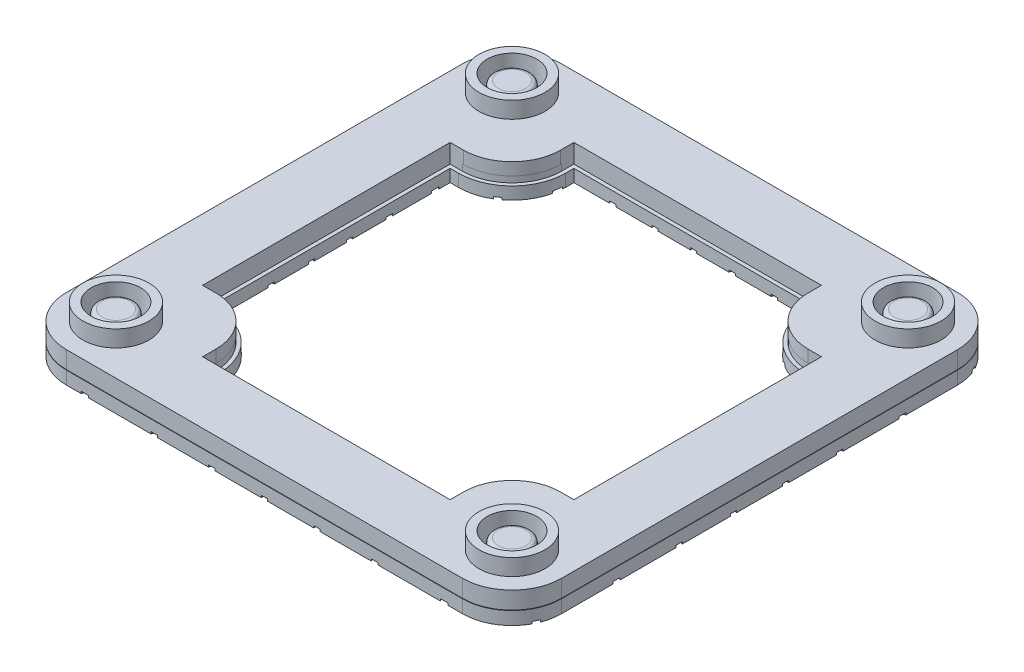
SolidWorks part; units mm, degrees
note: The reader was unsure of these and kept them because the rebuilt part matched: shared geometry of "Sketch3<4>".
ref_plane "Front Plane" through (0, 0, 0) normal (0, 0, 1) x (1, 0, 0)
ref_plane "Top Plane" through (0, 0, 0) normal (0, 1, 0) x (1, 0, 0)
ref_plane "Right Plane" through (0, 0, 0) normal (1, 0, 0) x (0, 0, -1)
sketch "Sketch1" plane through (0, 0, 0) normal (0, 1, 0) x (1, 0, 0)
  line L1 (0, 0) -> (240, 0)
  line L2 (0, 0) -> (0, 240)
  line L3 (0, 240) -> (240, 240)
  line L4 (240, 0) -> (240, 240)
  dimension "D1" = 240
  dimension "D2" = 240
extrude "Boss-Extrude1" add sketch "Sketch1" along normal blind 12
fillet "Fillet2" radius 24 4 edges at (240, 6, -240) (240, 6, 0) (0, 6, 0) (0, 6, -240)
sketch "Sketch3" plane through (0, 12, 0) normal (0, 1, 0) x (1, 0, 0)
  line L0 (24, 240) -> (24, 216) construction
  line L1 (24, 216) -> (216, 216) construction
  line L2 (216, 216) -> (216, 24) construction
  line L3 (216, 24) -> (24, 24) construction
  line L4 (24, 24) -> (24, 216) construction
  circle A0 centre (24, 216) radius 12
  circle A1 centre (216, 216) radius 12
  circle A2 centre (216, 24) radius 12
  circle A3 centre (24, 24) radius 12
  circle A4 centre (216, 216) radius 8.7
  circle A5 centre (216, 24) radius 8.7
  circle A6 centre (24, 24) radius 8.7
  circle A7 centre (24, 216) radius 8.7
  circle A8 centre (24, 216) radius 8.7
  circle A9 centre (216, 216) radius 8.7
  circle A10 centre (216, 24) radius 8.7
  circle A11 centre (24, 24) radius 8.7
  dimension "D1" = 24
  dimension "D2" = 24
  dimension "D3" = 24
  dimension "D4" = 24
  dimension "D5" = 17.4
  dimension "D6" = 17.4
  dimension "D7" = 17.4
  dimension "D8" = 17.4
extrude "Boss-Extrude2" add sketch "Sketch3<4>" along normal blind 5 contours A7 | A4 | A5 | A6
sketch "Sketch3<4>" plane through (0, 12, 0) normal (0, 1, 0) x (1, 0, 0) same geometry as "Sketch3"
extrude "Cut-Extrude2" cut sketch "Sketch3" against normal blind 6 contours A3 A6 | A2 A5 | A1 A4 | A0 A7
sketch "Sketch4" plane through (0, 0, 0) normal (0, -1, 0) x (1, 0, 0)
  line L0 (120, 0) -> (120, -240) construction
  line L1 (24, 0) -> (216, 0) construction
  line L2 (216, -240) -> (24, -240) construction
  line L3 (120, -240) -> (240, -120) construction
  line L4 (240, -24) -> (240, -216) construction
  line L5 (240, -120) -> (120, 0) construction
  line L6 (120, 0) -> (0, -120) construction
  line L7 (0, -216) -> (0, -24) construction
  line L8 (0, -120) -> (120, -240) construction
  line L9 (120, -240) -> (120, -120) construction
  line L10 (120, -120) -> (0, -120) construction
  line L11 (0, -120) -> (240, -120) construction
  line L12 (120, -120) -> (7.0294, -7.0294) construction
  line L13 (7.0294, -7.0294) -> (232.9706, -7.0294) construction
  line L14 (232.9706, -7.0294) -> (232.9706, -232.9706) construction
  line L15 (232.9706, -232.9706) -> (7.0294, -232.9706) construction
  line L16 (7.0294, -232.9706) -> (7.0294, -7.0294) construction
  line L17 (120, -120) -> (180, -180) construction
  line L18 (180, -180) -> (180, -60) construction
  line L19 (180, -60) -> (60, -60) construction
  line L20 (60, -60) -> (60, -180) construction
  line L21 (60, -180) -> (180, -60) construction
  line L22 (180, -60) -> (180, -180) construction
  line L23 (180, -180) -> (60, -180) construction
  line L24 (60, -180) -> (232.9706, -7.0294) construction
  line L25 (232.9706, -7.0294) -> (7.0294, -232.9706) construction
  line L26 (7.0294, -232.9706) -> (120, -120) construction
  line L27 (120, -120) -> (232.9706, -232.9706) construction
  line L29 (60, -240) -> (180, -240)
  line L30 (60, -240) -> (60, 0)
  line L31 (60, 0) -> (180, 0)
  line L32 (180, -240) -> (180, 0)
  line L33 (60, -240) -> (180, 0) construction
  line L34 (60, 0) -> (180, -240) construction
  line L35 (0, -180) -> (240, -180)
  line L36 (0, -180) -> (0, -60)
  line L37 (0, -60) -> (240, -60)
  line L38 (240, -180) -> (240, -60)
  line L39 (0, -180) -> (240, -60) construction
  line L40 (0, -60) -> (240, -180) construction
  arc A0 (24, 0) -> (0, -24) centre (24, -24) ccw construction
  arc A1 (240, -24) -> (216, 0) centre (216, -24) ccw construction
  arc A2 (216, -240) -> (240, -216) centre (216, -216) ccw construction
  arc A3 (0, -216) -> (24, -240) centre (24, -216) ccw construction
  line M1 (24, -240) -> (216, -240)
  line M3 (240, -216) -> (240, -24)
  line M5 (216, 0) -> (24, 0)
  line M7 (0, -24) -> (0, -216)
extrude "Cut-Extrude3" cut sketch "Sketch4" against normal blind 6 contours L37 L30 L35 L32 | L35 L30 L32 M1 | L37 L35 L30 M7 | L30 L37 L32 M5 | L37 L32 L35 M3
fillet "Fillet6" radius 24 12 edges at (60, 3, 0) (60, 3, -60) (0, 3, -60) (60, 3, -240) (60, 3, -180) (0, 3, -180) (180, 3, 0) (240, 3, -60) (180, 3, -60) (240, 3, -180) (180, 3, -240) (180, 3, -180)
sketch "Sketch5" plane through (0, 6, 0) normal (0, -1, 0) x (-1, 0, 0)
  line L0 (-30, 60) -> (-30, 180)
  line L1 (-24, 60) -> (-36, 60) construction
  line L2 (-24, 180) -> (-36, 180) construction
  line L3 (-60, 210) -> (-180, 210)
  line L4 (-60, 216) -> (-60, 204) construction
  line L5 (-180, 216) -> (-180, 204) construction
  line L6 (-210, 180) -> (-210, 60)
  line L7 (-204, 180) -> (-216, 180) construction
  line L8 (-180, 30) -> (-60, 30)
  line L9 (-180, 36) -> (-180, 24) construction
  line L10 (-60, 36) -> (-60, 24) construction
  line L11 (-30, 60) -> (-36.5, 60)
  line L12 (-60, 36.5) -> (-60, 30)
  line L13 (-180, 30) -> (-180, 36.5)
  line L14 (-203.5, 60) -> (-210, 60)
  line L15 (-210, 180) -> (-203.5, 180)
  line L16 (-180, 203.5) -> (-180, 210)
  line L17 (-30, 180) -> (-36.5, 180)
  line L18 (-60, 203.5) -> (-60, 210)
  line L19 (-210, 120) -> (-30, 120) construction
  line L20 (-180, 30) -> (-120, 80)
  line L21 (-210, 60) -> (-160, 120)
  line L22 (-210, 180) -> (-160, 120)
  line L23 (-180, 210) -> (-120, 160)
  line L24 (-60, 210) -> (-120, 160)
  line L25 (-30, 180) -> (-80, 120)
  line L26 (-80, 120) -> (-30, 60)
  line L27 (-60, 30) -> (-120, 80)
  arc A0 (-180, 36.5) -> (-203.5, 60) centre (-203.5, 36.5) ccw
  arc A1 (-203.5, 180) -> (-180, 203.5) centre (-203.5, 203.5) ccw
  arc A2 (-36.5, 180) -> (-60, 203.5) centre (-36.5, 203.5) cw
  arc A3 (-36.5, 60) -> (-60, 36.5) centre (-36.5, 36.5) ccw
  circle A4 centre (-120, 120) radius 40
  circle A5 centre (-120, 120) radius 25
  dimension "D1" = 23.5
  dimension "D2" = 80
  dimension "D3" = 50
extrude "Cut-Extrude4" cut sketch "Sketch5" against normal blind 6 contours L8 L27 L20 | L24 L3 L23 | L6 L19 L22 | L19 L6 L21 | L19 L26 L0 | L25 L19 L0 | L19 A5 | A5 L19
sketch "Sketch6" plane through (0, 12, 0) normal (0, 1, 0) x (1, 0, 0)
  line L1 (60, 210) -> (180, 210)
  line L2 (60, 210) -> (60, 30)
  line L3 (60, 30) -> (180, 30)
  line L4 (180, 210) -> (180, 30)
  line L5 (60, 210) -> (180, 30) construction
  line L6 (60, 30) -> (180, 210) construction
  point P0 (120, 120)
extrude "Cut-Extrude5" cut sketch "Sketch6" against normal blind 10
sketch "Sketch8" plane through (0, 12, 0) normal (0, 1, 0) x (1, 0, 0)
  line L0 (210, 180) -> (210, 60) construction
  line L1 (30, 180) -> (210, 180)
  line L2 (30, 180) -> (30, 60)
  line L3 (30, 60) -> (210, 60)
  line L4 (210, 180) -> (210, 60)
  line L5 (210, 60) -> (180, 96) construction
extrude "Cut-Extrude6" cut sketch "Sketch8" against normal blind 20
fillet "Fillet7" radius 23.5 4 edges at (180, 9, -60) (180, 9, -180) (60, 9, -60) (60, 9, -180)
sketch "Sketch9" plane through (0, 6, 0) normal (0, -1, 0) x (1, 0, 0)
  line L0 (60, -210) -> (96.9862, -218.9503) construction
  line L1 (36, -240) -> (204, -240) construction
  line L2 (96.9862, -225) -> (146.9862, -225) construction
  line L3 (96.9862, -210) -> (146.9862, -210)
  line L5 (96.9862, -240) -> (146.9862, -240)
  line L7 (121.9862, -225) -> (146.9862, -240) construction
  line L8 (96.9862, -240) -> (146.9862, -210) construction
  line L9 (96.9862, -210) -> (146.9862, -210)
  line L10 (96.9862, -240) -> (146.9862, -240)
  line L11 (121.9862, -225) -> (183.9723, -240) construction
  arc A0 (96.9862, -210) -> (96.9862, -240) centre (96.9862, -225) ccw
  arc A1 (146.9862, -240) -> (146.9862, -210) centre (146.9862, -225) ccw
  point P5 (121.9862, -225)
  point P12 (121.9862, -225)
  line M1 (180, -210) -> (60, -210)
  line M4 (36, -240) -> (204, -240)
  dimension "D1" = 50
extrude "Boss-Extrude4" add sketch "Sketch9" along normal blind 6 contours A1 A0 M4 M1
sketch "Sketch10" plane through (0, 6, 0) normal (0, -1, 0) x (1, 0, 0)
  line L0 (210, -120) -> (240, -120) construction
  line L1 (210, -180) -> (210, -60) construction
  line L2 (240, -204) -> (240, -36) construction
  line L3 (225, -95) -> (225, -145) construction
  line L5 (210, -95) -> (210, -145)
  line L7 (240, -95) -> (240, -145)
  line L8 (210, -95) -> (240, -145) construction
  line L9 (210, -145) -> (240, -95) construction
  line L10 (240, -95) -> (240, -145)
  line L11 (210, -95) -> (210, -145)
  arc A0 (240, -95) -> (210, -95) centre (225, -95) ccw
  arc A1 (210, -145) -> (240, -145) centre (225, -145) ccw
  point P6 (225, -120)
  point P13 (225, -120)
  line M1 (210, -60) -> (210, -180)
  line M4 (240, -204) -> (240, -36)
  dimension "D1" = 50
extrude "Boss-Extrude5" add sketch "Sketch10" along normal blind 6 contours A1 A0 M1 M4
sketch "Sketch11" plane through (0, 6, 0) normal (0, -1, 0) x (1, 0, 0)
  line L0 (120, 0) -> (120, -30) construction
  line L1 (204, 0) -> (36, 0) construction
  line L2 (180, -30) -> (60, -30) construction
  line L3 (95, -15) -> (145, -15) construction
  line L4 (95, 0) -> (145, 0)
  line L6 (95, -30) -> (145, -30)
  line L8 (95, 0) -> (145, -30) construction
  line L9 (95, -30) -> (145, 0) construction
  line L10 (95, 0) -> (145, 0)
  line L11 (95, -30) -> (145, -30)
  arc A0 (95, 0) -> (95, -30) centre (95, -15) ccw
  arc A1 (145, -30) -> (145, 0) centre (145, -15) ccw
  point P6 (120, -15)
  point P13 (120, -15)
  line M1 (60, -30) -> (180, -30)
  line M4 (204, 0) -> (36, 0)
  dimension "D1" = 50
extrude "Boss-Extrude6" add sketch "Sketch11" along normal blind 6 contours A1 A0 M1 M4
sketch "Sketch12" plane through (0, 6, 0) normal (0, -1, 0) x (1, 0, 0)
  line L0 (30, -120) -> (0, -120) construction
  line L1 (30, -60) -> (30, -180) construction
  line L2 (0, -36) -> (0, -204) construction
  line L3 (15, -95) -> (15, -145) construction
  line L5 (0, -95) -> (0, -145)
  line L7 (30, -95) -> (30, -145)
  line L8 (0, -95) -> (30, -145) construction
  line L9 (0, -145) -> (30, -95) construction
  line L10 (30, -95) -> (30, -145)
  line L11 (0, -95) -> (0, -145)
  arc A0 (30, -95) -> (0, -95) centre (15, -95) ccw
  arc A1 (0, -145) -> (30, -145) centre (15, -145) ccw
  point P6 (15, -120)
  point P13 (15, -120)
  line M1 (30, -180) -> (30, -60)
  line M4 (0, -36) -> (0, -204)
  dimension "D1" = 50
extrude "Boss-Extrude7" add sketch "Sketch12" along normal blind 6 contours A1 A0 M4 M1
fillet "Fillet8" radius 2 4 edges at (216, 17, -207.3) (24, 17, -207.3) (24, 17, -15.3) (216, 17, -15.3)
sketch "Sketch16" plane through (0, 12, 0) normal (0, 1, 0) x (1, 0, 0)
  circle A0 centre (24, 216) radius 12
  circle A1 centre (24, 216) radius 16
  dimension "D1" = 32
extrude "Boss-Extrude10" add sketch "Sketch16" along normal blind 8
sketch "Sketch17" plane through (0, 12, 0) normal (0, 1, 0) x (1, 0, 0)
  circle A0 centre (24, 24) radius 12
  circle A1 centre (24, 24) radius 16
  dimension "D1" = 32
extrude "Boss-Extrude11" add sketch "Sketch17" along normal blind 8
sketch "Sketch18" plane through (0, 12, 0) normal (0, 1, 0) x (1, 0, 0)
  circle A0 centre (216, 24) radius 12
  circle A1 centre (216, 24) radius 16
  circle A2 centre (216, 216) radius 12
  circle A3 centre (216, 216) radius 16
  dimension "D1" = 32
  dimension "D2" = 32
extrude "Boss-Extrude12" add sketch "Sketch18" along normal blind 8
sketch "Sketch19" plane through (0, 0, 0) normal (0, -1, 0) x (1, 0, 0)
  line L1 (36, 0) -> (204, 0)
  line L2 (36, 0) -> (36, -30)
  line L3 (36, -30) -> (204, -30)
  line L4 (204, 0) -> (204, -30)
  line L5 (0, -36) -> (30, -36)
  line L6 (0, -36) -> (0, -204)
  line L7 (0, -204) -> (30, -204)
  line L8 (30, -36) -> (30, -204)
  line L9 (36, -240) -> (204, -240)
  line L10 (36, -240) -> (36, -210)
  line L11 (36, -210) -> (204, -210)
  line L12 (204, -240) -> (204, -210)
  line L13 (240, -36) -> (210, -36)
  line L14 (240, -36) -> (240, -204)
  line L15 (240, -204) -> (210, -204)
  line L16 (210, -36) -> (210, -204)
extrude "Boss-Extrude13" add sketch "Sketch19" against normal blind 6 and the other way blind 0.0001
other "DeleteFace4" face at (50.4853, 3, -189.5147) face at (50.6835, 9, -189.3165)
sketch "Sketch20" plane through (0, 0, 0) normal (0, -1, 0) x (1, 0, 0)
  line L1 (276.3276, 37.736) -> (-46.6556, 37.736)
  line L2 (276.3276, 37.736) -> (276.3276, -265.5302)
  line L3 (276.3276, -265.5302) -> (-46.6556, -265.5302)
  line L4 (-46.6556, 37.736) -> (-46.6556, -265.5302)
  line L5 (276.3276, 37.736) -> (-46.6556, -265.5302) construction
  line L6 (276.3276, -265.5302) -> (-46.6556, 37.736) construction
  point P0 (114.836, -113.8971)
extrude "Cut-Extrude8" cut sketch "Sketch20" against normal blind 0.1 and the other way blind 10
sketch "Sketch21" plane through (0, 0.1, 0) normal (0, -1, 0) x (1, 0, 0)
  line L0 (62, -32) -> (62, -36)
  line L1 (178, -32) -> (62, -32)
  line L2 (178, -36) -> (178, -32)
  line L3 (208, -62) -> (204, -62)
  line L4 (240, -216) -> (240, -24)
  line L5 (216, 0) -> (24, 0)
  line L6 (0, -24) -> (0, -216)
  line L7 (24, -240) -> (216, -240)
  line L8 (240, -216) -> (240, -24)
  line L9 (216, 0) -> (24, 0)
  line L10 (0, -24) -> (0, -216)
  line L11 (24, -240) -> (216, -240)
  line L12 (30, -60) -> (30, -180)
  line L13 (36, -60) -> (30, -60)
  line L14 (60, -30) -> (60, -36)
  line L15 (180, -30) -> (60, -30)
  line L16 (180, -36) -> (180, -30)
  line L17 (210, -60) -> (204, -60)
  line L18 (210, -180) -> (210, -60)
  line L19 (204, -180) -> (210, -180)
  line L20 (180, -210) -> (180, -204)
  line L21 (60, -210) -> (180, -210)
  line L22 (60, -204) -> (60, -210)
  line L23 (30, -180) -> (36, -180)
  line L24 (30, -60) -> (30, -180) construction
  line L25 (36, -60) -> (30, -60) construction
  line L26 (60, -30) -> (60, -36) construction
  line L27 (180, -30) -> (60, -30) construction
  line L28 (180, -36) -> (180, -30) construction
  line L29 (210, -60) -> (204, -60) construction
  line L30 (210, -180) -> (210, -60) construction
  line L31 (204, -180) -> (210, -180) construction
  line L32 (180, -210) -> (180, -204) construction
  line L33 (60, -210) -> (180, -210) construction
  line L34 (60, -204) -> (60, -210) construction
  line L35 (30, -180) -> (36, -180) construction
  line L36 (208, -178) -> (208, -62)
  line L37 (204, -178) -> (208, -178)
  line L38 (178, -208) -> (178, -204)
  line L39 (62, -208) -> (178, -208)
  line L40 (62, -204) -> (62, -208)
  line L41 (32, -178) -> (36, -178)
  line L42 (32, -62) -> (32, -178)
  line L43 (36, -62) -> (32, -62)
  arc A0 (36, -62) -> (62, -36) centre (36, -36) ccw
  arc A1 (178, -36) -> (204, -62) centre (204, -36) ccw
  arc A2 (204, -178) -> (178, -204) centre (204, -204) ccw
  arc A3 (62, -204) -> (36, -178) centre (36, -204) ccw
  arc A4 (36, -60) -> (60, -36) centre (36, -36) ccw
  arc A5 (180, -36) -> (204, -60) centre (204, -36) ccw
  arc A6 (204, -180) -> (180, -204) centre (204, -204) ccw
  arc A7 (60, -204) -> (36, -180) centre (36, -204) ccw
  arc A8 (36, -60) -> (60, -36) centre (36, -36) ccw construction
  arc A9 (180, -36) -> (204, -60) centre (204, -36) ccw construction
  arc A10 (204, -180) -> (180, -204) centre (204, -204) ccw construction
  arc A11 (60, -204) -> (36, -180) centre (36, -204) ccw construction
  arc A12 (216, -240) -> (240, -216) centre (216, -216) ccw
  arc A13 (240, -24) -> (216, 0) centre (216, -24) ccw
  arc A14 (24, 0) -> (0, -24) centre (24, -24) ccw
  arc A15 (0, -216) -> (24, -240) centre (24, -216) ccw
  arc A16 (216, -240) -> (240, -216) centre (216, -216) ccw
  arc A17 (240, -24) -> (216, 0) centre (216, -24) ccw
  arc A18 (24, 0) -> (0, -24) centre (24, -24) ccw
  arc A19 (0, -216) -> (24, -240) centre (24, -216) ccw
  dimension "D1" = 0
  dimension "D2" = 0
  dimension "D3" = 2
extrude "Boss-Extrude14" add sketch "Sketch21" along normal blind 3 separate body
sketch "Sketch23" plane through (0, 0.1, 0) normal (0, 1, 0) x (1, 0, 0)
  line L0 (30.2, 179.8) -> (30.2, 60.2)
  line L1 (30.2, 60.2) -> (36, 60.2)
  line L2 (60.2, 36) -> (60.2, 30.2)
  line L3 (60.2, 30.2) -> (179.8, 30.2)
  line L4 (179.8, 30.2) -> (179.8, 36)
  line L5 (204, 60.2) -> (209.8, 60.2)
  line L6 (209.8, 60.2) -> (209.8, 179.8)
  line L7 (209.8, 179.8) -> (204, 179.8)
  line L8 (179.8, 204) -> (179.8, 209.8)
  line L9 (179.8, 209.8) -> (60.2, 209.8)
  line L10 (60.2, 209.8) -> (60.2, 204)
  line L11 (36, 179.8) -> (30.2, 179.8)
  line L12 (32, 62) -> (36, 62)
  line L13 (32, 178) -> (32, 62)
  line L14 (36, 178) -> (32, 178)
  line L15 (62, 208) -> (62, 204)
  line L16 (178, 208) -> (62, 208)
  line L17 (178, 204) -> (178, 208)
  line L18 (208, 178) -> (204, 178)
  line L19 (208, 62) -> (208, 178)
  line L20 (204, 62) -> (208, 62)
  line L21 (178, 32) -> (178, 36)
  line L22 (62, 32) -> (178, 32)
  line L23 (62, 36) -> (62, 32)
  line L24 (32, 62) -> (36, 62)
  line L25 (32, 178) -> (32, 62)
  line L26 (36, 178) -> (32, 178)
  line L27 (62, 208) -> (62, 204)
  line L28 (178, 208) -> (62, 208)
  line L29 (178, 204) -> (178, 208)
  line L30 (208, 178) -> (204, 178)
  line L31 (208, 62) -> (208, 178)
  line L32 (204, 62) -> (208, 62)
  line L33 (178, 32) -> (178, 36)
  line L34 (62, 32) -> (178, 32)
  line L35 (62, 36) -> (62, 32)
  arc A0 (60.2, 36) -> (36, 60.2) centre (36, 36) ccw
  arc A1 (204, 60.2) -> (179.8, 36) centre (204, 36) ccw
  arc A2 (179.8, 204) -> (204, 179.8) centre (204, 204) ccw
  arc A3 (36, 179.8) -> (60.2, 204) centre (36, 204) ccw
  arc A4 (62, 36) -> (36, 62) centre (36, 36) ccw
  arc A5 (36, 178) -> (62, 204) centre (36, 204) ccw
  arc A6 (178, 204) -> (204, 178) centre (204, 204) ccw
  arc A7 (204, 62) -> (178, 36) centre (204, 36) ccw
  arc A8 (62, 36) -> (36, 62) centre (36, 36) ccw
  arc A9 (36, 178) -> (62, 204) centre (36, 204) ccw
  arc A10 (178, 204) -> (204, 178) centre (204, 204) ccw
  arc A11 (204, 62) -> (178, 36) centre (204, 36) ccw
  dimension "D1" = 0
  dimension "D2" = 1.8
extrude "Boss-Extrude15" add sketch "Sketch23" along normal blind 3
sketch "Sketch24" plane through (0, -2.9, 0) normal (0, -1, 0) x (1, 0, 0)
  line L0 (32, -169.0748) -> (32, -172.5389)
  line L1 (171.7855, 0) -> (157.5382, -32)
  line L3 (118.5, 0) -> (118.5, -32)
  line L5 (121.5, 0) -> (121.5, -32)
  line L6 (118.9045, 0) -> (119.1966, -32) construction
  line L7 (118.9045, -240) -> (119.1966, -208) construction
  line L8 (175.0694, 0) -> (160.8221, -32)
  line L9 (237.0929, -12.5506) -> (188.1553, -56.6142)
  line L10 (238.4077, -15.4037) -> (190.7128, -58.3484)
  line L11 (240, -79.4324) -> (208, -89.8299)
  line L12 (240, -82.5868) -> (208, -92.9843)
  line L13 (240, -131.1042) -> (208, -127.7409)
  line L14 (240, -134.1208) -> (208, -130.7574)
  line L15 (240, -187.55) -> (208, -169.0748)
  line L16 (240, -191.0141) -> (208, -172.5389)
  line L17 (209.0392, -240) -> (178.6587, -198.1848)
  line L18 (205.331, -240) -> (178.0465, -202.4461)
  line L19 (147.0403, -240) -> (140.2385, -208)
  line L20 (143.9733, -240) -> (137.1715, -208)
  line L21 (96.0267, -240) -> (102.8285, -208)
  line L22 (92.9597, -240) -> (99.7615, -208)
  line L23 (34.669, -240) -> (61.9535, -202.4461)
  line L24 (30.9608, -240) -> (61.3413, -198.1848)
  line L25 (0, -191.0141) -> (32, -172.5389)
  line L26 (0, -187.55) -> (32, -169.0748)
  line L27 (0, -134.1208) -> (32, -130.7574)
  line L28 (0, -131.1042) -> (32, -127.7409)
  line L29 (0, -82.5868) -> (32, -92.9843)
  line L30 (0, -79.4324) -> (32, -89.8299)
  line L31 (1.5923, -15.4037) -> (49.2872, -58.3484)
  line L32 (2.9071, -12.5506) -> (51.8447, -56.6142)
  line L33 (64.9306, 0) -> (79.1779, -32)
  line L34 (68.2145, 0) -> (82.4618, -32)
  line L35 (190.7128, -181.6516) -> (238.4077, -224.5963)
  line L36 (188.1553, -183.3858) -> (237.0929, -227.4494)
  line L37 (0, -187.55) -> (0, -191.0141)
  line L38 (0, -157.4132) -> (0, -160.5676)
  line L39 (240, -216) -> (240, -24)
  line L40 (216, 0) -> (24, 0)
  line L41 (0, -24) -> (0, -216)
  line L42 (24, -240) -> (216, -240)
  line L43 (240, -191.0141) -> (240, -187.55)
  line L44 (209.0392, 0) -> (205.331, 0)
  line L45 (0, -48.9859) -> (0, -52.45)
  line L46 (30.9608, -240) -> (34.669, -240)
  line L47 (36, -62) -> (32, -62)
  line L48 (62, -32) -> (62, -36)
  line L49 (178, -32) -> (62, -32)
  line L50 (178, -36) -> (178, -32)
  line L51 (208, -62) -> (204, -62)
  line L52 (208, -178) -> (208, -62)
  line L53 (204, -178) -> (208, -178)
  line L54 (178, -208) -> (178, -204)
  line L55 (62, -208) -> (178, -208)
  line L56 (62, -204) -> (62, -208)
  line L57 (32, -178) -> (36, -178)
  line L58 (32, -62) -> (32, -178)
  line L61 (160.8221, -32) -> (157.5382, -32)
  line L64 (208, -172.5389) -> (208, -169.0748)
  line L67 (79.1779, -208) -> (82.4618, -208)
  line L70 (32, -67.4611) -> (32, -70.9252)
  line L71 (160.8221, -208) -> (175.0694, -240)
  line L72 (157.5382, -208) -> (171.7855, -240)
  line L73 (32, -147.0157) -> (32, -150.1701)
  line L74 (99.7615, -208) -> (102.8285, -208)
  line L75 (121.5, -208) -> (121.5, -240)
  line L76 (120.8034, -208) -> (121.0955, -240) construction
  line L77 (92.9597, -240) -> (96.0267, -240)
  line L78 (118.5, -208) -> (118.5, -240)
  line L79 (64.9306, -240) -> (68.2145, -240)
  line L80 (118.5, -208) -> (121.5, -208)
  line L81 (82.4618, -208) -> (68.2145, -240)
  line L82 (79.1779, -208) -> (64.9306, -240)
  line L83 (118.5, -240) -> (121.5, -240)
  line L84 (137.1715, -208) -> (140.2385, -208)
  line L85 (51.8447, -183.3858) -> (2.9071, -227.4494)
  line L86 (49.2872, -181.6516) -> (1.5923, -224.5963)
  line L87 (143.9733, -240) -> (147.0403, -240)
  line L88 (171.7855, -240) -> (175.0694, -240)
  line L89 (32, -150.1701) -> (0, -160.5676)
  line L90 (32, -147.0157) -> (0, -157.4132)
  line L91 (157.5382, -208) -> (160.8221, -208)
  line L92 (205.331, -240) -> (209.0392, -240)
  line L93 (32, -112.2591) -> (0, -108.8958)
  line L94 (32, -109.2426) -> (0, -105.8792)
  line L95 (208, -150.1701) -> (208, -147.0157)
  line L96 (240, -160.5676) -> (240, -157.4132)
  line L97 (32, -70.9252) -> (0, -52.45)
  line L98 (32, -67.4611) -> (0, -48.9859)
  line L99 (240, -134.1208) -> (240, -131.1042)
  line L100 (208, -130.7574) -> (208, -127.7409)
  line L101 (61.3413, -41.8152) -> (30.9608, 0)
  line L102 (61.9535, -37.5539) -> (34.669, 0)
  line L103 (208, -112.2591) -> (208, -109.2426)
  line L104 (240, -108.8958) -> (240, -105.8792)
  line L105 (99.7615, -32) -> (92.9597, 0)
  line L106 (102.8285, -32) -> (96.0267, 0)
  line L107 (240, -82.5868) -> (240, -79.4324)
  line L108 (208, -92.9843) -> (208, -89.8299)
  line L109 (120.8034, -32) -> (121.0955, 0) construction
  line L110 (240, -52.45) -> (240, -48.9859)
  line L111 (137.1715, -32) -> (143.9733, 0)
  line L112 (140.2385, -32) -> (147.0403, 0)
  line L113 (208, -70.9252) -> (208, -67.4611)
  line L114 (82.4618, -32) -> (79.1779, -32)
  line L115 (178.0465, -37.5539) -> (205.331, 0)
  line L116 (178.6587, -41.8152) -> (209.0392, 0)
  line L119 (208, -67.4611) -> (240, -48.9859)
  line L120 (208, -70.9252) -> (240, -52.45)
  line L123 (208, -109.2426) -> (240, -105.8792)
  line L124 (208, -112.2591) -> (240, -108.8958)
  line L127 (208, -147.0157) -> (240, -157.4132)
  line L128 (208, -150.1701) -> (240, -160.5676)
  line L131 (34.669, 0) -> (30.9608, 0)
  line L132 (68.2145, 0) -> (64.9306, 0)
  line L133 (96.0267, 0) -> (92.9597, 0)
  line L134 (102.8285, -32) -> (99.7615, -32)
  line L135 (121.5, -32) -> (118.5, -32)
  line L136 (121.5, 0) -> (118.5, 0)
  line L137 (147.0403, 0) -> (143.9733, 0)
  line L138 (140.2385, -32) -> (137.1715, -32)
  line L139 (175.0694, 0) -> (171.7855, 0)
  line L140 (32, -89.8299) -> (32, -92.9843)
  line L141 (0, -79.4324) -> (0, -82.5868)
  line L142 (32, -109.2426) -> (32, -112.2591)
  line L143 (0, -105.8792) -> (0, -108.8958)
  line L144 (0, -131.1042) -> (0, -134.1208)
  line L145 (32, -127.7409) -> (32, -130.7574)
  arc A0 (188.1553, -56.6142) -> (190.7128, -58.3484) centre (204, -36) ccw
  arc A1 (61.3413, -41.8152) -> (61.9535, -37.5539) centre (36, -36) ccw
  arc A4 (51.8447, -183.3858) -> (49.2872, -181.6516) centre (36, -204) ccw
  arc A5 (178.6587, -198.1848) -> (178.0465, -202.4461) centre (204, -204) ccw
  arc A8 (36, -62) -> (62, -36) centre (36, -36) ccw
  arc A9 (178, -36) -> (204, -62) centre (204, -36) ccw
  arc A10 (204, -178) -> (178, -204) centre (204, -204) ccw
  arc A11 (62, -204) -> (36, -178) centre (36, -204) ccw
  arc A12 (49.2872, -58.3484) -> (51.8447, -56.6142) centre (36, -36) ccw
  arc A13 (178.0465, -37.5539) -> (178.6587, -41.8152) centre (204, -36) ccw
  arc A14 (190.7128, -181.6516) -> (188.1553, -183.3858) centre (204, -204) ccw
  arc A15 (61.9535, -202.4461) -> (61.3413, -198.1848) centre (36, -204) ccw
  arc A16 (216, -240) -> (240, -216) centre (216, -216) ccw
  arc A17 (240, -24) -> (216, 0) centre (216, -24) ccw
  arc A18 (24, 0) -> (0, -24) centre (24, -24) ccw
  arc A19 (0, -216) -> (24, -240) centre (24, -216) ccw
  arc A20 (237.0929, -227.4494) -> (238.4077, -224.5963) centre (216, -216) ccw
  arc A21 (238.4077, -15.4037) -> (237.0929, -12.5506) centre (216, -24) ccw
  arc A22 (2.9071, -12.5506) -> (1.5923, -15.4037) centre (24, -24) ccw
  arc A23 (1.5923, -224.5963) -> (2.9071, -227.4494) centre (24, -216) ccw
  dimension "D3" = 0
  dimension "D4" = 0
  dimension "D2" = 15
extrude "Cut-Extrude10" cut sketch "Sketch24" against normal blind 1
chamfer "Chamfer1" distance 3.5 angle 45 8 edges at (0, 0.1, -120) (7.0294, 0.1, -7.0294) (7.0294, 0.1, -232.9706) (120, 0.1, 0) (120, 0.1, -240) (232.9706, 0.1, -7.0294) (232.9706, 0.1, -232.9706) (240, 0.1, -120)
sketch "Sketch27" plane through (0, 0.1, 0) normal (0, 1, 0) x (1, 0, 0)
  line L0 (3.3, 216) -> (3.3, 24)
  line L1 (24, 3.3) -> (216, 3.3)
  line L2 (236.7, 24) -> (236.7, 216)
  line L3 (216, 236.7) -> (24, 236.7)
  line L8 (3.5, 216) -> (3.5, 24)
  line L9 (216, 236.5) -> (24, 236.5)
  line L10 (236.5, 24) -> (236.5, 216)
  line L11 (24, 3.5) -> (216, 3.5)
  line L12 (3.5, 216) -> (3.5, 24) construction
  line L13 (216, 236.5) -> (24, 236.5) construction
  line L14 (236.5, 24) -> (236.5, 216) construction
  line L15 (24, 3.5) -> (216, 3.5) construction
  line L18 (216, 240) -> (24, 240)
  line L19 (0, 216) -> (0, 24)
  line L20 (24, 0) -> (216, 0)
  line L21 (240, 24) -> (240, 216)
  line L22 (216, 240) -> (24, 240)
  line L23 (0, 216) -> (0, 24)
  line L24 (24, 0) -> (216, 0)
  line L25 (240, 24) -> (240, 216)
  arc A0 (3.3, 24) -> (24, 3.3) centre (24, 24) ccw
  arc A1 (216, 3.3) -> (236.7, 24) centre (216, 24) ccw
  arc A2 (236.7, 216) -> (216, 236.7) centre (216, 216) ccw
  arc A3 (24, 236.7) -> (3.3, 216) centre (24, 216) ccw
  arc A8 (3.5, 24) -> (24, 3.5) centre (24, 24) ccw
  arc A9 (24, 236.5) -> (3.5, 216) centre (24, 216) ccw
  arc A10 (236.5, 216) -> (216, 236.5) centre (216, 216) ccw
  arc A11 (216, 3.5) -> (236.5, 24) centre (216, 24) ccw
  arc A12 (3.5, 24) -> (24, 3.5) centre (24, 24) ccw construction
  arc A13 (24, 236.5) -> (3.5, 216) centre (24, 216) ccw construction
  arc A14 (236.5, 216) -> (216, 236.5) centre (216, 216) ccw construction
  arc A15 (216, 3.5) -> (236.5, 24) centre (216, 24) ccw construction
  arc A18 (240, 216) -> (216, 240) centre (216, 216) ccw
  arc A19 (24, 240) -> (0, 216) centre (24, 216) ccw
  arc A20 (0, 24) -> (24, 0) centre (24, 24) ccw
  arc A21 (216, 0) -> (240, 24) centre (216, 24) ccw
  arc A22 (240, 216) -> (216, 240) centre (216, 216) ccw
  arc A23 (24, 240) -> (0, 216) centre (24, 216) ccw
  arc A24 (0, 24) -> (24, 0) centre (24, 24) ccw
  arc A25 (216, 0) -> (240, 24) centre (216, 24) ccw
  dimension "D1" = 0
  dimension "D2" = 0.2
  dimension "D3" = 0
extrude "Boss-Extrude17" add sketch "Sketch27" along normal blind 3.3
chamfer "Chamfer2" distance 3.2 angle 45 8 edges at (236.7, 3.4, -120) (230.6371, 3.4, -230.6371) (230.6371, 3.4, -9.3629) (120, 3.4, -236.7) (120, 3.4, -3.3) (9.3629, 3.4, -230.6371) (9.3629, 3.4, -9.3629) (3.3, 3.4, -120)
sketch "Sketch28" plane through (0, 0.1, 0) normal (0, -1, 0) x (1, 0, 0)
  line L0 (120, -210) -> (120, -128.2529) construction
  line L1 (60, -210) -> (180, -210) construction
